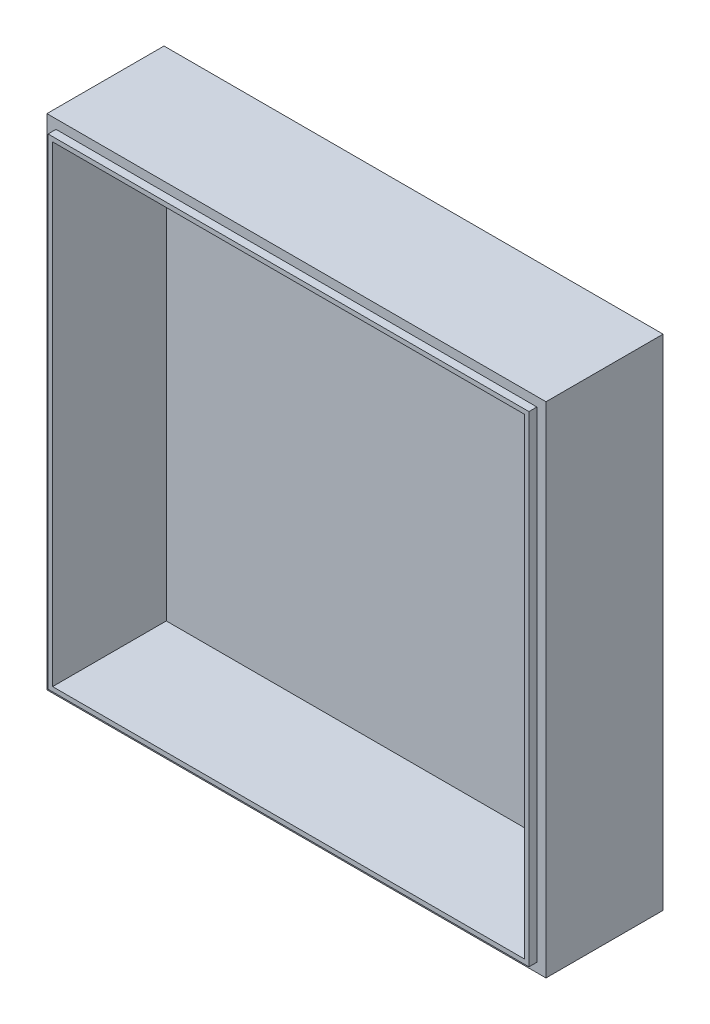
SolidWorks part; units mm, degrees
ref_plane "Front Plane" through (0, 0, 0) normal (0, 0, 1) x (1, 0, 0)
ref_plane "Top Plane" through (0, 0, 0) normal (0, 1, 0) x (1, 0, 0)
ref_plane "Right Plane" through (0, 0, 0) normal (1, 0, 0) x (0, 0, -1)
sketch "Sketch1" plane through (0, 0, 0) normal (0, 0, 1) x (1, 0, 0)
  line L0 (-2.4, -2.4) -> (85.4, -2.4)
  line L1 (0, 0) -> (83, 0)
  line L2 (0, 0) -> (0, 83)
  line L3 (0, 83) -> (83, 83)
  line L4 (83, 0) -> (83, 83)
  line L5 (85.4, -2.4) -> (85.4, 85.4)
  line L6 (-2.4, 85.4) -> (85.4, 85.4)
  line L7 (-2.4, -2.4) -> (-2.4, 85.4)
  dimension "D1" = 83
  dimension "D2" = 2.4
extrude "Boss-Extrude1" add sketch "Sketch1" against normal blind 2 contours L6 L5 L0 L7
extrude "Boss-Extrude2" add sketch "Sketch1<3>" along normal blind 20
sketch "Sketch1<3>" plane through (0, 0, 0) normal (0, 0, 1) x (1, 0, 0) same geometry as "Sketch1"
sketch "Sketch2" plane through (0, 0, 20) normal (0, 0, 1) x (1, 0, 0)
  line L0 (83, 83) -> (0, 83) construction
  line L1 (-0.8, 83.8) -> (83.8, 83.8)
  line L2 (-0.8, 83.8) -> (-0.8, -0.8)
  line L3 (-0.8, -0.8) -> (83.8, -0.8)
  line L4 (83.8, 83.8) -> (83.8, -0.8)
  line L5 (83, 0) -> (83, 83) construction
  point P4 (41.5, 83.8)
  point P7 (41.5, 83)
  point P8 (83.8, 41.5)
  point P11 (83, 41.5)
  dimension "D1" = 0.8
  dimension "D2" = 0.8
extrude "Cut-Extrude1" cut sketch "Sketch2" against normal blind 1.4 flip side to cut
